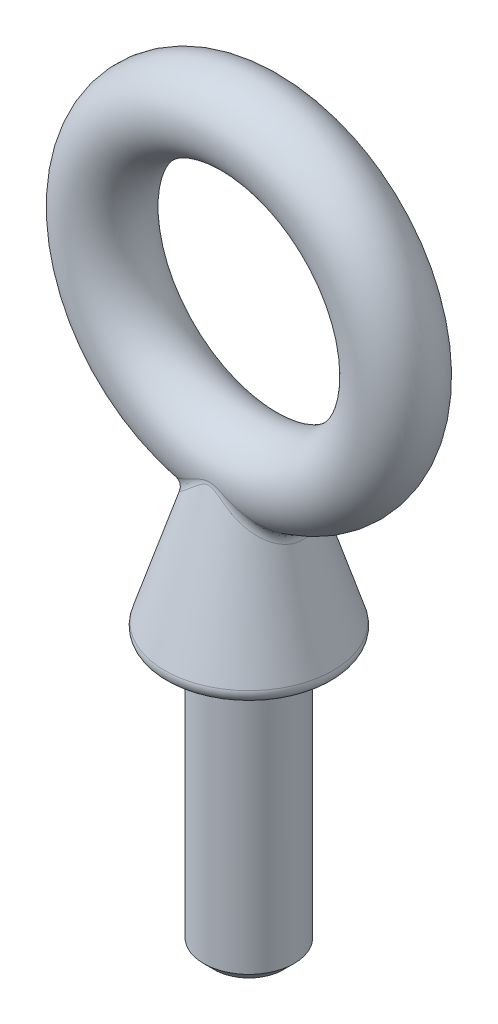
SolidWorks part; units mm, degrees
ref_plane "Front Plane" through (0, 0, 0) normal (0, 0, 1) x (1, 0, 0)
ref_plane "Top Plane" through (0, 0, 0) normal (0, 1, 0) x (1, 0, 0)
ref_plane "Right Plane" through (0, 0, 0) normal (1, 0, 0) x (0, 0, -1)
sketch "Sketch1" plane through (0, 0, 0) normal (0, 0, 1) x (1, 0, 0)
  line L0 (0, -26.1937) -> (0, -80.1688) construction
  line L1 (-6.35, -80.1688) -> (6.35, -80.1688) construction
  line L2 (6.5615, -80.0466) -> (6.5615, -82.0005) construction
  line L3 (0, -26.1937) -> (0, -15.0812) construction
  line L4 (-11.9062, -42.0687) -> (11.9063, -42.0687) construction
  line L5 (6.5615, -82.0005) -> (4.8694, -81.0236) construction
  line L6 (4.8694, -81.0236) -> (6.5615, -80.0466) construction
  line L7 (4.8694, -81.0236) -> (5.0809, -81.0236) construction
  line L8 (6.5615, -81.0236) -> (6.35, -81.0236) construction
  line L9 (5.0809, -81.1457) -> (5.0809, -80.9014) construction
  line L10 (6.35, -81.8784) -> (6.35, -80.1688) construction
  line L11 (6.4558, -81.9394) -> (6.4558, -80.1077) construction
  circle A0 centre (0, 0) radius 26.1937 construction
  circle A1 centre (0, 20.6375) radius 5.5562 construction
  circle A2 centre (0, 0) radius 15.0813 construction
  point P7 (0, -26.1937)
  point P9 (0, -42.0687)
  point P10 (0, 26.1937)
  point P11 (0, 15.0812)
  point P14 (0, -80.1688)
  point P17 (0, 0)
  point P19 (0, -20.6375)
  point P21 (0, -42.0687)
  point P32 (5.0809, -81.0236)
  point P35 (6.35, -81.0236)
  point P38 (6.4558, -81.0236)
  dimension "Pitch" = 1.9538
  dimension "D1" = 0.2442
sketch "Sketch2" plane through (0, 0, 0) normal (0, 1, 0) x (1, 0, 0)
  circle A0 centre (0, 0) radius 6.35
extrude "Boss-Extrude1" add sketch "Sketch2" against normal up to vertex (80.1688 mm away) from vertex up to point (0, -80.1688, 0) starting at point (0, -42.0687, 0)
sketch "Sketch3" plane through (0, -80.1688, 0) normal (0, -1, 0) x (1, 0, 0)
  circle A1 centre (0, 0) radius 6.35
  circle A2 centre (0, 0) radius 6.35
  point P0 (6.35, 0)
  point P1 (0, -6.35)
  dimension "D1" = 0
sketch "Sketch4" plane through (0, 0, 0) normal (0, 0, 1) x (1, 0, 0)
  line L0 (5.0809, -80.9014) -> (5.0809, -81.1457)
  line L1 (5.0809, -81.1457) -> (6.4558, -81.9394)
  line L2 (6.4558, -81.9394) -> (6.4558, -80.1077)
  line L3 (6.4558, -80.1077) -> (5.0809, -80.9014)
sketch "Sketch5" plane through (0, -80.1688, 0) normal (0, -1, 0) x (1, 0, 0)
  circle A0 centre (0, 0) radius 4.8694
extrude "Cut-Extrude1" cut sketch "Sketch5" against normal through all draft 45 flip side to cut
sketch "Sketch6" plane through (0, 0, 0) normal (1, 0, 0) x (0, 0, -1)
  circle A0 centre (0, 20.6375) radius 5.5563
ref_axis "Axis1" through (0, 0, -7.6398) along (0, 0, 1)
revolve "Revolve1" add sketch "Sketch6" angle 360 about axis through (0, 0, -7.6398) along (0, 0, 1)
sketch "Sketch8" plane through (0, 0, 0) normal (0, 0, 1) x (1, 0, 0)
  line L0 (0, -42.0687) -> (0, -20.6375)
  line L1 (0, -20.6375) -> (-5.5562, -20.6375)
  line L2 (-10.5172, -42.0687) -> (-11.9062, -42.0687) construction
  line L3 (-11.9062, -42.0687) -> (-11.9062, -40.6797) construction
  line L4 (0, -42.0687) -> (11.9062, -42.0687) construction
  line L5 (-11.9062, -42.0687) -> (11.9063, -42.0687) construction
  line L6 (-11.84, -40.256) -> (-5.5562, -20.6375)
  line L7 (-11.9062, -42.0687) -> (0, -42.0687) construction
  line L9 (-10.5172, -42.0687) -> (0, -42.0687)
  arc A0 (-11.84, -40.256) -> (-10.5172, -42.0687) centre (-10.5172, -40.6797) ccw
  circle A1 centre (0, -20.6375) radius 5.5562 construction
  dimension "D1" = 1.3891
revolve "Revolve2" add sketch "Sketch8" angle 360 about L0
fillet "Fillet1" radius 1.3891 1 edges at (6.2964, -24.6961, 2.7135)
sketch "SketchX" plane through (0, 0, 0) normal (1, 0, 0) x (0, 0, -1)
  line L0 (6.35, -80.1688) -> (6.35, -75.2841) construction
  line L1 (0, -80.1688) -> (6.35, -80.1688) construction
  dimension "D1" = 4.8846
  dimension "D2" = 6.35
ref_axis "Center Axis 1" through (0, 21.5506, 0) along (0, -1, 0)
ref_axis "Center Axis 2" through (0, 0, -7.6398) along (0, 0, 1)
equation "\"D1@Sketch1\"=\"Pitch@Sketch1\"/8"
equation "\"Pitch@Helix/Spiral1\"=\"Pitch@Sketch1\""
equation "\"D2@SketchX\" = \"Thread OD@Sketch1\" / 2"
